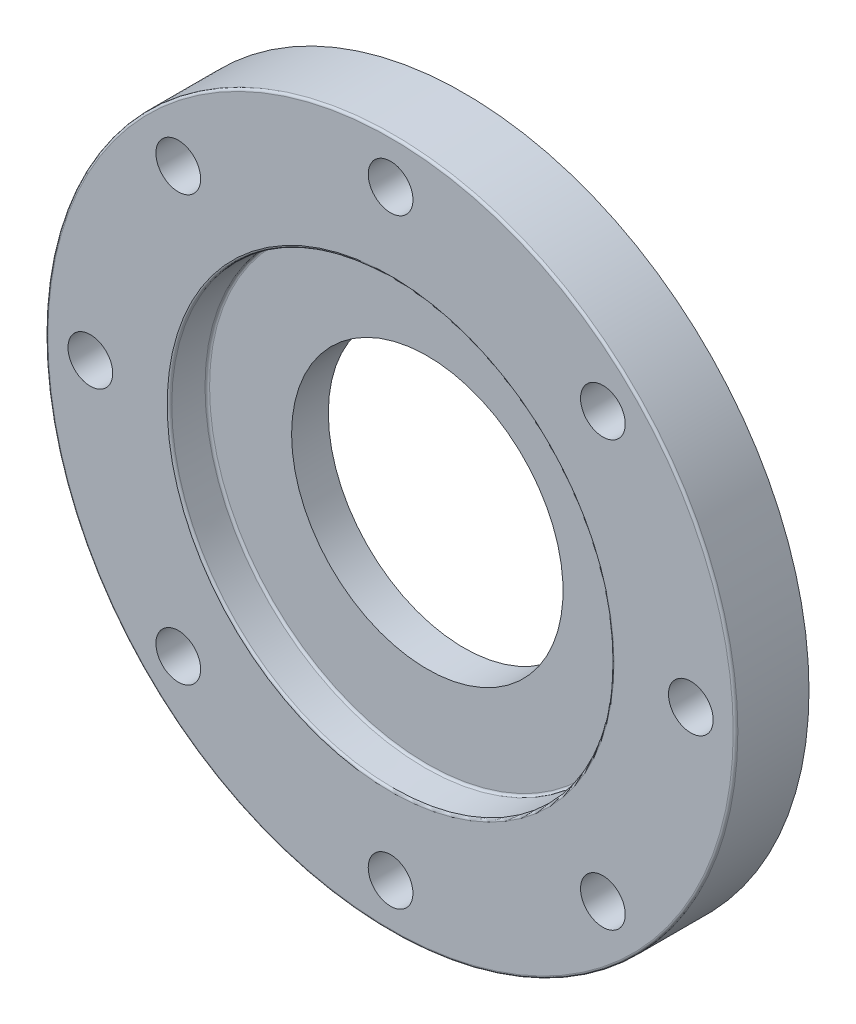
SolidWorks part; units mm, degrees
ref_plane "Front Plane" through (0, 0, 0) normal (0, 0, 1) x (1, 0, 0)
ref_plane "Top Plane" through (0, 0, 0) normal (0, 1, 0) x (1, 0, 0)
ref_plane "Right Plane" through (0, 0, 0) normal (1, 0, 0) x (0, 0, -1)
sketch "Sketch0" plane through (0, 0, 0) normal (1, 0, 0) x (0, 0, -1)
  line L0 (0, 0) -> (-36.5125, 0) construction
  point P3 (-36.5125, 0)
  point P4 (-5.5562, 0)
  dimension "Q" = 36.5125
  dimension "N" = 5.5562
sketch "Sketch1" plane through (0, 0, 0) normal (0, 0, 1) x (1, 0, 0)
  circle A0 centre (0, 0) radius 171.45
  circle A1 centre (0, 0) radius 109.9185 construction
  circle A2 centre (0, 0) radius 149.225 construction
  circle A3 centre (0, 149.225) radius 11.1125 construction
  circle A6 centre (0, 0) radius 109.347 construction
  point P9 (0, 109.9185)
  point P10 (0, 109.347)
  dimension "A" = 342.9
  dimension "B" = 298.45
  dimension "Bolt Hole Size" = 22.225
  dimension "Pipe OD A" = 219.837
  dimension "Pipe OD B" = 218.694
extrude "Extrude1" add sketch "Sketch1" along normal up to vertex (36.5125 mm away) up to point (0, 0, 36.5125)
sketch "Sketch2" plane through (0, 0, 36.5125) normal (0, 0, 1) x (1, 0, 0)
  circle A0 centre (0, 149.225) radius 11.1125 construction
  circle A1 centre (0, 149.225) radius 11.1125
extrude "Extrude2" cut sketch "Sketch2" against normal through all
ref_axis "Axis1" through (0, 0, -1.6272) along (0, 0, 1)
pattern_circular "CirPattern1" count 8 over 360 about axis through (0, 0, -1.6272) along (0, 0, 1) of "Extrude2"
sketch "Sketch3" plane through (0, 0, 0) normal (1, 0, 0) x (0, 0, -1)
  line L0 (-36.5125, 109.9185) -> (-18.2563, 109.347)
  line L1 (-18.2563, 109.347) -> (-18.2562, 0)
  line L2 (0, 0) -> (-36.5125, 0) construction
  line L3 (-18.2562, 0) -> (-36.5125, 0)
  line L4 (-36.5125, 0) -> (-36.5125, 109.9185)
  line L5 (0, 109.347) -> (-18.2563, 109.347) construction
  line L6 (-36.5125, 109.9185) -> (0, 109.9185) construction
revolve "Cut-Revolve1" cut sketch "Sketch3" angle 360 about L3
fillet "Fillet1" radius 1.1545 3 edges at (171.45, 0, 36.5125) (0, 109.347, 18.2563) (0, 109.9185, 36.5125) tangent propagation no
sketch "Sketch5" plane through (0, 0, 0) normal (0, 0, -1) x (-1, 0, 0)
  circle A0 centre (0, 0) radius 67.4624
  dimension "D1" = 134.9248
extrude "Cut-Extrude1" cut sketch "Sketch5" against normal blind 237.236 contours A0
